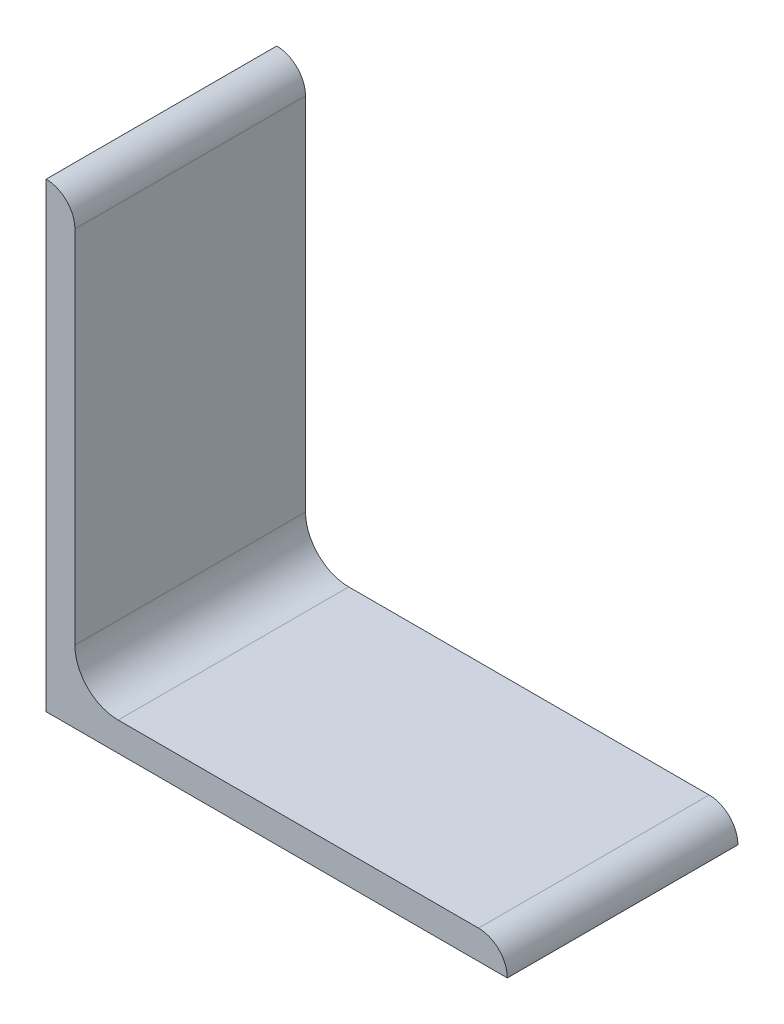
SolidWorks part; units mm, degrees
ref_plane "Plane1" through (0, 0, 0) normal (0, 0, 1) x (1, 0, 0)
ref_plane "Plane2" through (0, 0, 0) normal (0, 1, 0) x (1, 0, 0)
ref_plane "Plane3" through (0, 0, 0) normal (1, 0, 0) x (0, 0, -1)
sketch "Sketch1" plane through (0, 0, 0) normal (0, 0, 1) x (1, 0, 0)
  line L0 (0, 0) -> (0, 50.8)
  line L1 (0, 50.8) -> (0.0051, 50.8)
  line L2 (3.175, 47.6301) -> (3.175, 7.9375)
  line L3 (7.9375, 3.175) -> (47.6301, 3.175)
  line L4 (50.8, 0.0051) -> (50.8, 0)
  line L5 (50.8, 0) -> (0, 0)
  arc A0 (50.8, 0.0051) -> (47.6301, 3.175) centre (47.6301, 0.0051) ccw
  arc A1 (0.0051, 50.8) -> (3.175, 47.6301) centre (0.0051, 47.6301) cw
  arc A2 (7.9375, 3.175) -> (3.175, 7.9375) centre (7.9375, 7.9375) cw
  circle A3 centre (0, 0) radius 3.175 construction
  dimension "D1" = 3.175
  dimension "V_leg" = 50.8
  dimension "H_leg" = 50.8
  dimension "D2" = 0.0051
extrude "BaseSteelAngle" add sketch "Sketch1" along normal mid plane 25.4
equation "\"Flat_wid@Sketch1\" = ((sgn(\"Thickness@Sketch1\" - \"Radius_2@Sketch1\") +1)*(\"Thickness@Sketch1\" - \"Radius_2@Sketch1\"))/2 +0.0002"
equation "\"D1@Sketch1\" = \"Thickness@Sketch1\""
equation "\"D2@Sketch1\" = \"Flat_wid@Sketch1\""
